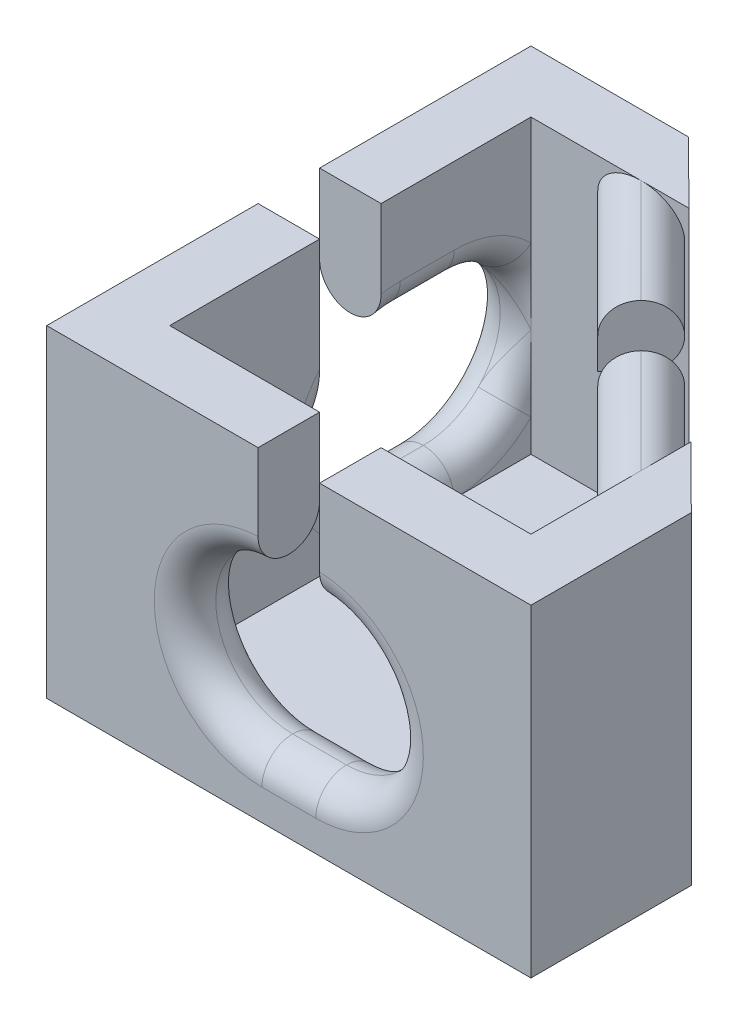
SolidWorks part; units mm, degrees
ref_plane "Front Plane" through (0, 0, 0) normal (0, 0, 1) x (1, 0, 0)
ref_plane "Top Plane" through (0, 0, 0) normal (0, 1, 0) x (1, 0, 0)
ref_plane "Right Plane" through (0, 0, 0) normal (1, 0, 0) x (0, 0, -1)
sketch "Sketch1" plane through (0, 0, 0) normal (0, 1, 0) x (1, 0, 0)
  line L0 (0, 15.75) -> (15.75, 0) construction
  line L1 (0, 0) -> (15.75, 0)
  line L2 (0, 0) -> (0, 15.75)
  line L3 (0, 15.75) -> (15.75, 15.75)
  line L4 (15.75, 0) -> (15.75, 15.75)
  circle A0 centre (7.875, 7.875) radius 1.25
  dimension "D2" = 2.5
  dimension "D1" = 15.75
extrude "BaseBoss-Extrude1" add sketch "Sketch1" along normal blind 1
sketch "Sketch2" plane through (0, 1, 0) normal (0, 1, 0) x (1, 0, 0)
  line L0 (0, 15.75) -> (0, 0) construction
  line L1 (0, 15.75) -> (15.75, 15.75)
  line L2 (0, 15.75) -> (0, 0)
  line L3 (0, 0) -> (15.75, 0)
  line L4 (15.75, 15.75) -> (15.75, 0)
  line L6 (2, 13.75) -> (13.75, 13.75)
  line L7 (2, 13.75) -> (2, 2)
  line L8 (2, 2) -> (13.75, 2)
  line L9 (13.75, 13.75) -> (13.75, 2)
  dimension "D1" = 2
  dimension "D2" = 2
  dimension "D3" = 2
  dimension "D4" = 2
extrude "WallsBoss-Extrude2" add sketch "Sketch2" along normal blind 7.5
sketch "AngleSketch3" plane through (0, 8.5, 0) normal (0, 1, 0) x (1, 0, 0)
  line L0 (7, 13.75) -> (13.75, 7)
  line L1 (13.75, 13.75) -> (2, 13.75) construction
  line L2 (13.75, 2) -> (13.75, 13.75) construction
  line L3 (13.75, 2) -> (13.75, 13.75) construction
  line L4 (4.1716, 13.75) -> (13.75, 4.1716)
  line L5 (13.75, 13.75) -> (2, 13.75) construction
  line L6 (0, 15.75) -> (0, 0) construction
  line L7 (0, 15.75) -> (15.75, 15.75)
  line L8 (0, 15.75) -> (0, 0)
  line L9 (0, 0) -> (15.75, 0)
  line L10 (15.75, 15.75) -> (15.75, 0)
  line L11 (15.75, 15.75) -> (0, 15.75) construction
  line L12 (4.1716, 13.75) -> (2, 13.75)
  line L13 (2, 13.75) -> (2, 2)
  line L14 (2, 2) -> (13.75, 2)
  line L15 (13.75, 2) -> (13.75, 4.1716)
  line L16 (7, 13.75) -> (13.75, 13.75)
  line L17 (13.75, 13.75) -> (13.75, 7)
  dimension "D3" = 2
  dimension "D1" = 9.5459
  dimension "D2" = 45
extrude "AngleBoss-Extrude3" add sketch "AngleSketch3" along normal blind 2
sketch "Sketch4" plane through (0, 0, 0) normal (-1, 0, 0) x (0, 0, 1)
  line L0 (-11.25, 4.5) -> (-9.5, 4.5) construction
  line L1 (-11.25, 7) -> (-9.5, 7)
  line L2 (-11.25, 2) -> (-9.5, 2)
  line L3 (-15.75, 0) -> (0, 0) construction
  line L4 (-15.75, 10.5) -> (-15.75, 0) construction
  arc A0 (-11.25, 7) -> (-11.25, 2) centre (-11.25, 4.5) ccw
  arc A1 (-9.5, 2) -> (-9.5, 7) centre (-9.5, 4.5) ccw
  point P2 (-10.375, 4.5)
  dimension "D2" = 2
  dimension "D1" = 5
  dimension "D3" = 4.5
  dimension "D4" = 1.75
extrude "InCut-Extrude1" cut sketch "Sketch4" against normal blind 2
sketch "Sketch5" plane through (0, 0, 0) normal (0, 0, 1) x (1, 0, 0)
  line L0 (7, 4.5) -> (8.75, 4.5) construction
  line L1 (7, 7) -> (8.75, 7)
  line L2 (7, 2) -> (8.75, 2)
  line L3 (0, 10.5) -> (0, 0) construction
  line L4 (0, 0) -> (15.75, 0) construction
  arc A0 (7, 7) -> (7, 2) centre (7, 4.5) ccw
  arc A1 (8.75, 2) -> (8.75, 7) centre (8.75, 4.5) ccw
  point P2 (7.875, 4.5)
  dimension "D4" = 2
  dimension "D1" = 5
  dimension "D2" = 1.75
extrude "OutCut-Extrude2" cut sketch "Sketch5" against normal blind 2
sketch "Sketch7" plane through (0, 10.5, 0) normal (0, 1, 0) x (1, 0, 0)
  line L0 (5.121, 15.75) -> (15.75, 5.215)
  line L1 (15.75, 15.75) -> (0, 15.75) construction
  line L2 (15.75, 0) -> (15.75, 15.75) construction
  line L3 (15.75, 5.215) -> (15.75, 15.75)
  line L4 (15.75, 15.75) -> (5.121, 15.75)
extrude "Cut-Extrude2" cut sketch "Sketch7" against normal through all
fillet "InFillet1" radius 1 4 edges at (0, 4.5, -13.75) (0, 7, -10.375) (0, 4.5, -7) (0, 2, -10.375)
fillet "OutFillet2" radius 1 4 edges at (11.25, 4.5, 0) (7.875, 2, 0) (4.5, 4.5, 0) (7.875, 7, 0)
fillet "InFillet3" radius 1 5 edges at (2, 2.7322, -13.0178) (2, 6.2678, -13.0178) (2, 7, -10.375) (2, 4.5, -7) (2, 2, -10.375)
fillet "OutFillet4" radius 1 4 edges at (11.25, 4.5, -2) (7.875, 2, -2) (4.5, 4.5, -2) (7.875, 7, -2)
sketch "Sketch6" plane through (0, 10.5, 0) normal (0, 1, 0) x (1, 0, 0)
  line L0 (0, 15.75) -> (0, 0) construction
  line L1 (0, 8.875) -> (2, 8.875)
  line L2 (0, 8.875) -> (0, 6.875)
  line L3 (0, 6.875) -> (2, 6.875)
  line L4 (2, 8.875) -> (2, 6.875)
  line L5 (2, 2) -> (13.75, 2) construction
  line L6 (6.875, 2) -> (8.875, 2)
  line L7 (6.875, 2) -> (6.875, 0)
  line L8 (6.875, 0) -> (8.875, 0)
  line L9 (8.875, 2) -> (8.875, 0)
  line L10 (0, 0) -> (15.75, 0) construction
  line L11 (2, 13.75) -> (2, 2) construction
  line L12 (5.121, 15.75) -> (0, 15.75) construction
  line L13 (8.2537, 9.6679) -> (9.6679, 8.2537)
  line L14 (13.75, 4.1716) -> (4.1716, 13.75) construction
  line L15 (9.6679, 8.2537) -> (11.0821, 9.6679)
  line L16 (7, 13.75) -> (13.75, 7) construction
  line L17 (11.0821, 9.6679) -> (9.6679, 11.0821)
  line L18 (9.6679, 11.0821) -> (8.2537, 9.6679)
  dimension "D2" = 6.875
  dimension "D3" = 6.875
  dimension "D4" = 3.773
extrude "Cut-Extrude1" cut sketch "Sketch6" against normal blind 7
fillet "Fillet5" radius 1 2 edges at (12.4161, 10.5, -8.3339) (8.3339, 10.5, -12.4161)
fillet "Fillet6" radius 1 2 edges at (11.7089, 10.5, -6.2126) (6.2126, 10.5, -11.7089)
fillet "Fillet7" radius 1 2 edges at (12.4161, 8.5, -8.3339) (8.3339, 8.5, -12.4161)
equation "\"D1@Sketch1\"=\"ClampWidth\""
equation "\"RibbonCableWidth\"= 6.75mm"
equation "\"RibbonCableInnerHypotonus\"= sqr ( \"RibbonCableWidth\" ^ 2 * 2 )"
equation "\"M2.5HoleDiameter\"= 2.5mm"
equation "\"FastenerTabHoleCenterFromSide\"= 2mm"
equation "\"ClampWallWidth\"= 2mm"
equation "\"ClampWidth\"= \"RibbonCableWidth\" + \"ClampWallWidth\" * 2 + \"RibbonCableWidthExtension\""
equation "\"ClampHeight\"= \"BaseBoss\" + \"RibbonCableUpperWallHeight\" + \"ClampBridgeHeight\""
equation "\"BaseBoss\"= 1mm"
equation "\"RibbonCableLowerWallHeight\"= 2mm"
equation "\"RibbonCableOuterHypotonus\"= sqr ( ( \"ClampWallWidth\" ^ 2 ) * 2 ) + \"RibbonCableInnerHypotonus\" + sqr ( ( \"ClampWallWidth\" ^ 2 ) * 2 )"
equation "\"2W3HRibbonCableHeight\"= 5mm'Two strands wide, 3 strands stacked up"
equation "\"D1@BaseBoss-Extrude1\" = \"BaseBoss\""
equation "\"D1@Sketch2\"=\"ClampWallWidth\""
equation "\"D2@Sketch2\"=\"ClampWallWidth\""
equation "\"D3@Sketch2\"=\"ClampWallWidth\""
equation "\"D4@Sketch2\"=\"ClampWallWidth\""
equation "\"D1@WallsBoss-Extrude2\"=\"RibbonCableUpperWallHeight\""
equation "\"D1@AngleSketch3\" = \"RibbonCableInnerHypotonus\""
equation "\"RibbonCableWidthExtension\"= 5mm"
equation "\"D3@AngleSketch3\" = \"ClampWallWidth\""
equation "\"D1@AngleBoss-Extrude3\" = \"ClampWallWidth\""
equation "\"D2@Sketch1\"=\"M2.5HoleDiameter\""
equation "\"D1@Sketch4\"=\"2W3HRibbonCableHeight\""
equation "\"D2@Sketch4\"=\"RibbonCableLowerWallHeight\""
equation "\"D3@Sketch4\"=\"2W3HRibbonCableHeight\"/2 + \"ClampWallWidth\""
equation "\"D4@Sketch4\"=\"RibbonCableWidth\" - \"2W3HRibbonCableHeight\""
equation "\"D1@InCut-Extrude1\" = \"ClampWallWidth\""
equation "\"D1@Sketch5\"=\"2W3HRibbonCableHeight\""
equation "\"D2@Sketch5\"=\"RibbonCableWidth\"-\"2W3HRibbonCableHeight\""
equation "\"D3@Sketch5\"=(\"ClampWidth\" - \"RibbonCableWidth\" + \"2W3HRibbonCableHeight\")/2 "
equation "\"D1@OutCut-Extrude2\" = \"ClampWallWidth\""
equation "\"ClampBridgeHeight\"= 2mm"
equation "\"RibbonCableUpperWallHeight\"= \"RibbonCableLowerWallHeight\" + \"2W3HRibbonCableHeight\" + .5mm"
equation "\"D1@Sketch6\"=\"RibbonCableOpeningWidth\""
equation "\"D2@Sketch6\"= \"ClampWidth\"/2 - \"RibbonCableOpeningWidth\" / 2"
equation "\"D3@Sketch6\"=\"ClampWidth\"/2 - \"RibbonCableOpeningWidth\"/2"
equation "\"D4@Sketch6\"=(\"RibbonCableInnerHypotonus\" - \"RibbonCableOpeningWidth\" )/2"
equation "\"D1@Cut-Extrude1\"=\"2W3HRibbonCableHeight\" + 2mm"
equation "\"RibbonCableOpeningWidth\"= 2mm"
equation "\"D4@Sketch5\"=\"RibbonCableLowerWallHeight\""
